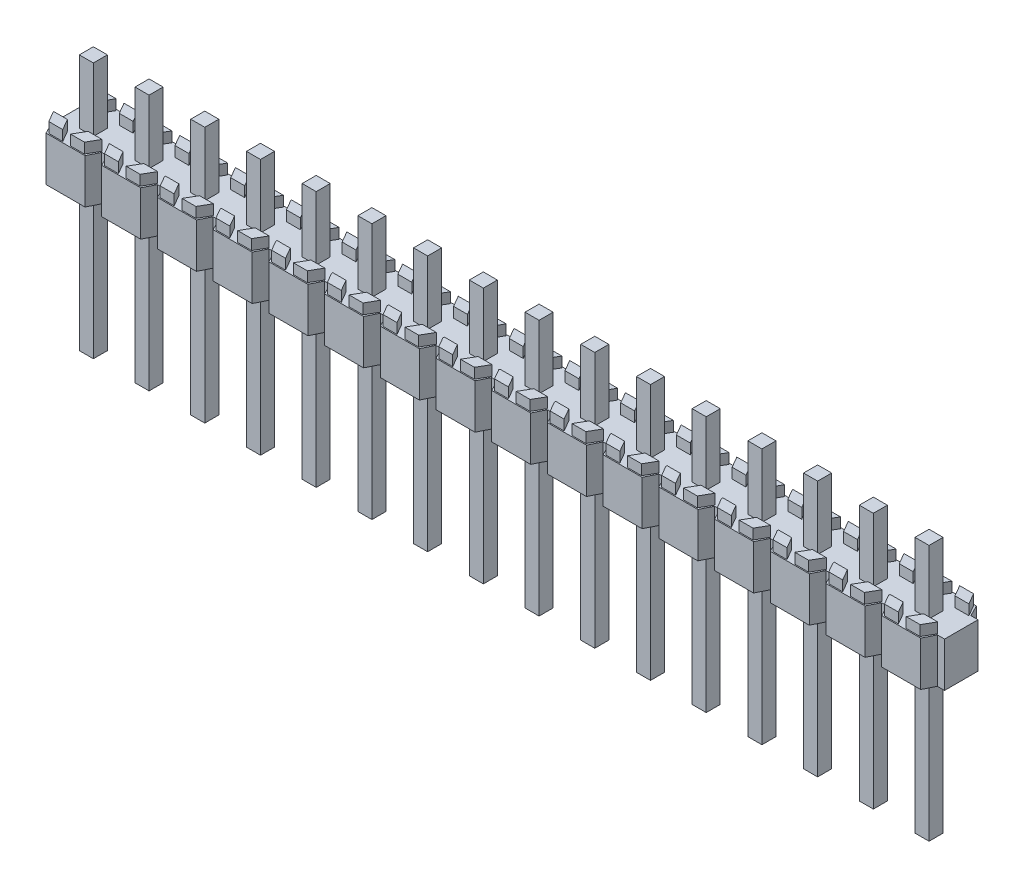
SolidWorks part; units mm, degrees
ref_plane "Front Plane" through (0, 0, 0) normal (0, 0, 1) x (1, 0, 0)
ref_plane "Top Plane" through (0, 0, 0) normal (0, 1, 0) x (1, 0, 0)
ref_plane "Right Plane" through (0, 0, 0) normal (1, 0, 0) x (0, 0, -1)
sketch "Sketch1" plane through (0, 0, 0) normal (0, 1, 0) x (1, 0, 0)
  line L0 (0, 1.5791) -> (0, -1.5527) construction
  line L2 (-0.32, 0.32) -> (0.32, 0.32)
  line L3 (-0.32, 0.32) -> (-0.32, -0.32)
  line L4 (-0.32, -0.32) -> (0.32, -0.32)
  line L5 (0.32, 0.32) -> (0.32, -0.32)
  line L6 (-0.32, 0.32) -> (0.32, -0.32) construction
  line L7 (-0.32, -0.32) -> (0.32, 0.32) construction
  line L8 (-1.143, 0.762) -> (-0.889, 1.27)
  line L9 (-0.889, 1.27) -> (0.889, 1.27)
  line L10 (0.889, 1.27) -> (1.143, 0.762)
  line L11 (1.143, 0.762) -> (1.47, 0.762)
  line L12 (1.47, 0.762) -> (1.47, -0.762)
  line L13 (1.47, -0.762) -> (1.143, -0.762)
  line L14 (1.143, -0.762) -> (0.889, -1.27)
  line L15 (0.889, -1.27) -> (-0.889, -1.27)
  line L16 (-0.889, -1.27) -> (-1.143, -0.762)
  line L17 (-1.143, -0.762) -> (-1.143, 0.762)
  line L18 (-1.7519, 0.762) -> (1.5375, 0.762) construction
  line L19 (1.0554, 0) -> (-1.5628, 0) construction
  line L20 (-1.697, -0.762) -> (2.4529, -0.762) construction
  point P3 (0, 0)
  dimension "D1" = 0.64
  dimension "D2" = 0.64
  dimension "D3" = 0.889
  dimension "D4" = 1.778
  dimension "D5" = 1.27
  dimension "D6" = 1.143
  dimension "D7" = 0.762
  dimension "D8" = 1.47
extrude "Boss-Extrude1" add sketch "Sketch1" along normal blind 1.48 and the other way blind 1.02
sketch "Sketch2" plane through (0, 1.48, 0) normal (0, 1, 0) x (1, 0, 0)
  line L0 (-1.1061, -0.7112) -> (-0.4711, -0.7112)
  line L1 (-0.4711, -0.7112) -> (-0.1778, -1.2192)
  line L2 (-0.1778, -1.2192) -> (-0.8128, -1.2192)
  line L3 (-1.143, 0.762) -> (-1.143, -0.762) construction
  line L4 (-0.889, 1.27) -> (-1.143, 0.762) construction
  line L5 (-0.8128, -1.2192) -> (-1.1061, -0.7112)
  line L6 (0, 1.3694) -> (0, -1.4569) construction
  line L7 (-1.5186, 0) -> (1.896, 0) construction
  line L8 (-0.8128, 1.2192) -> (-1.1061, 0.7112)
  line L9 (-0.1778, 1.2192) -> (-0.8128, 1.2192)
  line L10 (-0.4711, 0.7112) -> (-0.1778, 1.2192)
  line L11 (-1.1061, 0.7112) -> (-0.4711, 0.7112)
  line L12 (1.1061, 0.7112) -> (0.4711, 0.7112)
  line L13 (0.4711, 0.7112) -> (0.1778, 1.2192)
  line L14 (0.1778, 1.2192) -> (0.8128, 1.2192)
  line L15 (0.8128, 1.2192) -> (1.1061, 0.7112)
  line L16 (0.8128, -1.2192) -> (1.1061, -0.7112)
  line L17 (0.1778, -1.2192) -> (0.8128, -1.2192)
  line L18 (0.4711, -0.7112) -> (0.1778, -1.2192)
  line L19 (1.1061, -0.7112) -> (0.4711, -0.7112)
  line L20 (0.889, 1.27) -> (-0.889, 1.27) construction
  line L21 (1.143, 0.762) -> (0.889, 1.27) construction
  line L22 (1.47, 0.762) -> (1.143, 0.762) construction
  line L23 (1.47, -0.762) -> (1.47, 0.762) construction
  line L24 (1.143, -0.762) -> (1.47, -0.762) construction
  line L25 (0.889, -1.27) -> (1.143, -0.762) construction
  line L26 (-0.889, -1.27) -> (0.889, -1.27) construction
  line L27 (-1.143, -0.762) -> (-0.889, -1.27) construction
  line L28 (-1.143, 0.762) -> (-1.143, -0.762)
  line L29 (-0.889, 1.27) -> (-1.143, 0.762)
  line L30 (0.889, 1.27) -> (-0.889, 1.27)
  line L31 (1.143, 0.762) -> (0.889, 1.27)
  line L32 (1.47, 0.762) -> (1.143, 0.762)
  line L33 (1.47, -0.762) -> (1.47, 0.762)
  line L34 (1.143, -0.762) -> (1.47, -0.762)
  line L35 (0.889, -1.27) -> (1.143, -0.762)
  line L36 (-0.889, -1.27) -> (0.889, -1.27)
  line L37 (-1.143, -0.762) -> (-0.889, -1.27)
extrude "Cut-Extrude2" cut sketch "Sketch2" against normal blind 0.47
sketch "Sketch3" plane through (0, 1.01, 0) normal (0, 1, 0) x (1, 0, 0)
  line L4 (-0.32, 0.32) -> (0.32, 0.32)
  line L5 (0.32, 0.32) -> (0.32, -0.32)
  line L6 (0.32, -0.32) -> (-0.32, -0.32)
  line L7 (-0.32, -0.32) -> (-0.32, 0.32)
extrude "Boss-Extrude2" add sketch "Sketch3" along normal blind 2.9 separate body
sketch "Sketch4" plane through (0, -1.02, 0) normal (0, -1, 0) x (1, 0, 0)
  line L4 (-0.32, -0.32) -> (0.32, -0.32)
  line L5 (0.32, -0.32) -> (0.32, 0.32)
  line L6 (0.32, 0.32) -> (-0.32, 0.32)
  line L7 (-0.32, 0.32) -> (-0.32, -0.32)
  line L8 (-0.32, -0.32) -> (0.32, -0.32)
  line L9 (0.32, -0.32) -> (0.32, 0.32)
  line L10 (0.32, 0.32) -> (-0.32, 0.32)
  line L11 (-0.32, 0.32) -> (-0.32, -0.32)
  dimension "D1" = 0
extrude "Boss-Extrude3" add sketch "Sketch4" along normal blind 6.75 separate body
pattern_linear "LPattern1" count 16 spacing 2.54 along (1, 0, 0) of "Boss-Extrude1", "Cut-Extrude2", "Boss-Extrude2", "Boss-Extrude3"
